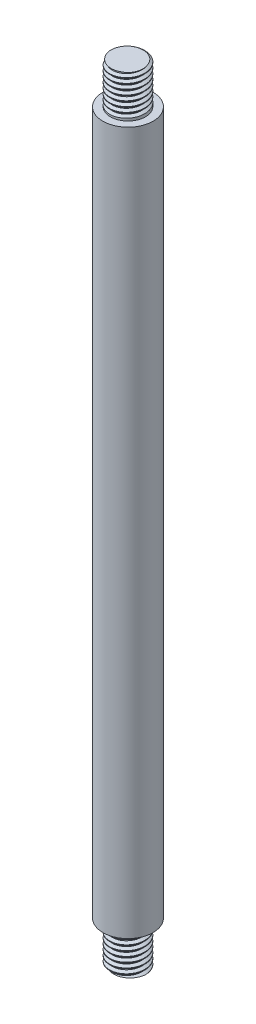
SolidWorks part; units mm, degrees
ref_plane "Front Plane" through (0, 0, 0) normal (0, 0, 1) x (1, 0, 0)
ref_plane "Top Plane" through (0, 0, 0) normal (0, 1, 0) x (1, 0, 0)
ref_plane "Right Plane" through (0, 0, 0) normal (1, 0, 0) x (0, 0, -1)
sketch "Sketch1" plane through (0, 0, 0) normal (0, 1, 0) x (1, 0, 0)
  line L0 (0, 0) -> (-10716.1472, 0) construction
  line L1 (0, 0) -> (0, -10716.1472) construction
  circle A0 centre (0, 0) radius 3.5
  circle A1 centre (0, 0) radius 5
  dimension "D1" = 7
  dimension "D2" = 10
extrude "Boss-Extrude1" add sketch "Sketch1" along normal mid plane 156 contours A0 region at (0, 0, 0)
extrude "Boss-Extrude2" add sketch "Sketch1<5>" along normal mid plane 140
sketch "Sketch1<5>" plane through (0, 0, 0) normal (0, 1, 0) x (1, 0, 0) same geometry as "Sketch1"
thread "Thread2" pitch 1 method cut profile "Thread Profile3" start angle 0, offset 1, length 8, pitch 1, diameter 7
ref_plane "Plane3" through (3.5, -79, 0) normal (0, 0, 1) x (1, 0, 0)
sketch "Thread Profile3" plane through (3.5, -79, 0) normal (0, 0, 1) x (1, 0, 0)
  line L0 (0, 0) -> (0, 1) construction
  line L11 (0, 0) -> (0, 0.875)
  line L12 (0, 0.875) -> (-0.5413, 0.5625)
  line L13 (-0.5413, 0.5625) -> (-0.5413, 0.3125)
  line L15 (-0.5413, 0.3125) -> (0, 0)
  line L17 (-0.5413, 0.4375) -> (0, 0.4375) construction
  point P2 (0, 0)
  dimension "Pitch" = 1
  dimension "Profile_Angle" = 60
  dimension "Profile_Land" = 0.25
  dimension "Profile_Height" = 0.5413
thread "Thread3" pitch 1 method cut profile "Thread Profile4" start angle 0, offset 1, length 8, pitch 1, diameter 7
ref_plane "Plane4" through (-3.5, 79, 0) normal (0, 0, 1) x (-1, 0, 0)
sketch "Thread Profile4" plane through (-3.5, 79, 0) normal (0, 0, 1) x (-1, 0, 0)
  line L0 (0, 0) -> (0, 1) construction
  line L11 (0, 0) -> (0, 0.875)
  line L12 (0, 0.875) -> (-0.5413, 0.5625)
  line L13 (-0.5413, 0.5625) -> (-0.5413, 0.3125)
  line L15 (-0.5413, 0.3125) -> (0, 0)
  line L17 (-0.5413, 0.4375) -> (0, 0.4375) construction
  point P2 (0, 0)
  dimension "Pitch" = 1
  dimension "Profile_Angle" = 60
  dimension "Profile_Land" = 0.25
  dimension "Profile_Height" = 0.5413
